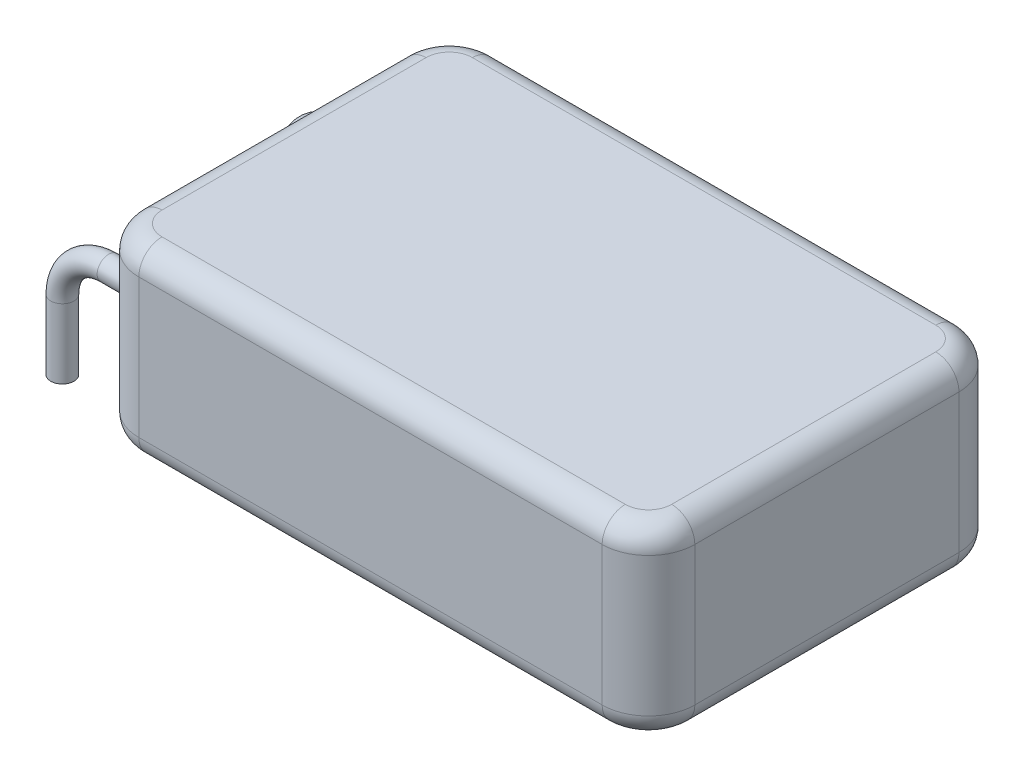
SolidWorks part; units mm, degrees
ref_plane "Спереди" through (0, 0, 0) normal (0, 0, 1) x (1, 0, 0)
ref_plane "Сверху" through (0, 0, 0) normal (0, 1, 0) x (1, 0, 0)
ref_plane "Справа" through (0, 0, 0) normal (1, 0, 0) x (0, 0, -1)
sketch "Эскиз1" plane through (0, 0, 0) normal (0, 1, 0) x (1, 0, 0)
  line L1 (-5, 3.85) -> (5, 3.85)
  line L2 (-6, 2.85) -> (-6, -2.85)
  line L3 (-5, -3.85) -> (5, -3.85)
  line L4 (6, 2.85) -> (6, -2.85)
  line L5 (-6, 3.85) -> (6, -3.85) construction
  line L6 (-6, -3.85) -> (6, 3.85) construction
  arc A0 (-5, 3.85) -> (-6, 2.85) centre (-5, 2.85) ccw
  arc A1 (-5, -3.85) -> (-6, -2.85) centre (-5, -2.85) cw
  arc A2 (5, -3.85) -> (6, -2.85) centre (5, -2.85) ccw
  arc A3 (6, 2.85) -> (5, 3.85) centre (5, 2.85) ccw
  point P0 (0, 0)
  dimension "D3" = 1
  dimension "D1" = 7.7
  dimension "D2" = 12
extrude "Бобышка-Вытянуть1" add sketch "Эскиз1" along normal blind 4
sketch "Эскиз2" plane through (-6, 0, 0) normal (-1, 0, 0) x (0, 0, 1)
  line L0 (-2.85, 2) -> (2.85, 2) construction
  line L1 (-2.85, 4) -> (-2.85, 0) construction
  line L2 (2.85, 4) -> (2.85, 0) construction
  line L3 (0, 4) -> (0, 0) construction
  line L4 (-2.85, 4) -> (2.85, 4) construction
  line L5 (2.5, 4) -> (2.5, 0) construction
  line L6 (-2.85, 0) -> (2.85, 0) construction
  circle A0 centre (-2.5, 2) radius 0.25
  circle A1 centre (2.5, 2) radius 0.25
  point P15 (0, 2)
  point P20 (0, 0)
  dimension "D6" = 0.5
  dimension "D7" = 0.5
  dimension "D1" = 2.85
  dimension "D2" = 4
  dimension "D3" = 2.85
  dimension "D4" = 2.5
  dimension "D5" = 2.5
sketch3d "Трехмерный эскиз1"
  line L0 (-6, 2, 2.5) -> (-7, 2, 2.5)
  line L1 (-8, 1, 2.5) -> (-8, -0.5, 2.5)
  line L2 (-6, 2, -2.5) -> (-7, 2, -2.5)
  line L3 (-8, 1, -2.5) -> (-8, -0.5, -2.5)
  arc A0 (-8, 1, 2.5) -> (-7, 2, 2.5) centre (-7, 1, 2.5) ccw
  arc A1 (-8, 1, -2.5) -> (-7, 2, -2.5) centre (-7, 1, -2.5) ccw
  point P6 (-8, 2, 2.5)
  point P7 (-7, 1, 1.5)
  point P14 (-8, 2, -2.5)
  point P15 (-7, 1, -3.5)
  dimension "D2" = 1
  dimension "D6" = 1
  dimension "D1" = 2
  dimension "D3" = 2.5
  dimension "D4" = 2
  dimension "D5" = 2.5
sweep "По траектории4" add profiles "Эскиз2" path "Трехмерный эскиз1"
fillet "Скругление1" radius 0.5 8 edges at (5.7071, 4, -3.5571) (6, 4, 0) (5.7071, 4, 3.5571) (0, 4, 3.85) (-5.7071, 4, 3.5571) (-6, 4, 0) (-5.7071, 4, -3.5571) (0, 4, -3.85)
fillet "Скругление2" radius 0.5 8 edges at (5.7071, 0, -3.5571) (6, 0, 0) (5.7071, 0, 3.5571) (0, 0, 3.85) (-5.7071, 0, 3.5571) (-6, 0, 0) (-5.7071, 0, -3.5571) (0, 0, -3.85)
